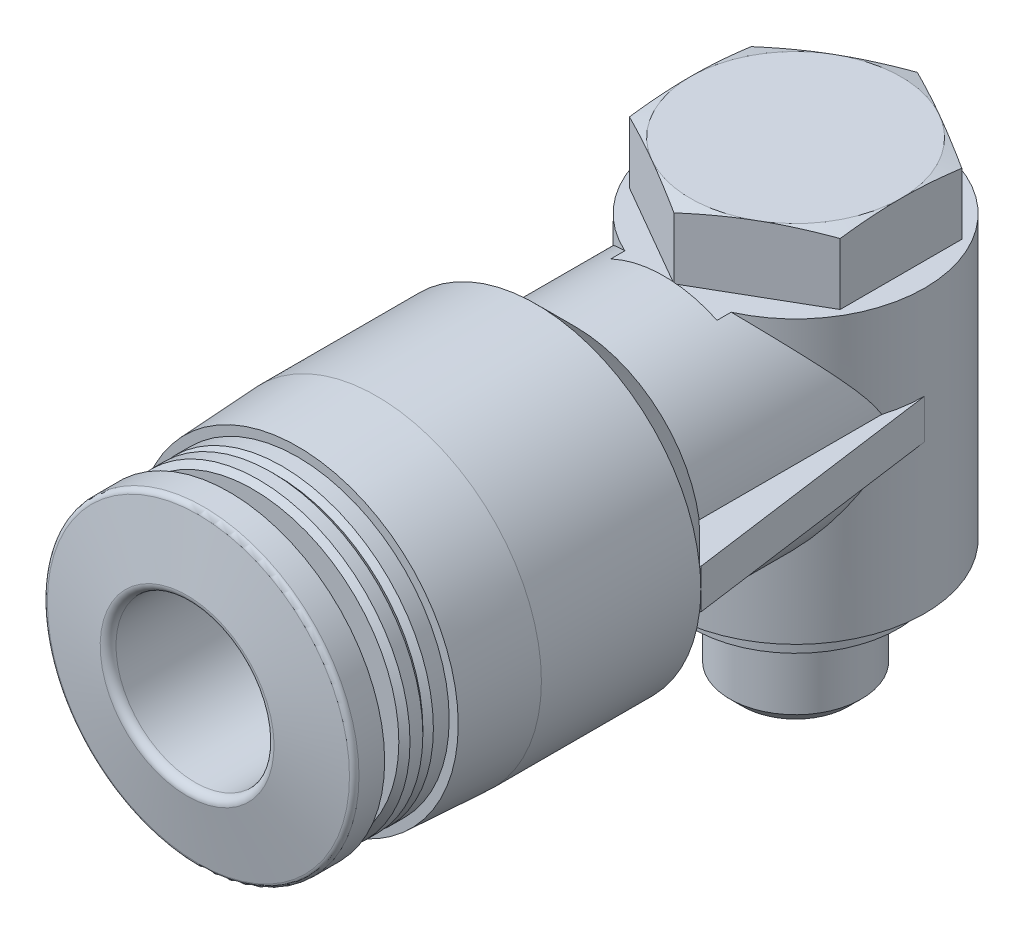
SolidWorks part; units mm, degrees
ref_plane "Ebene vorne" through (0, 0, 0) normal (0, 0, 1) x (1, 0, 0)
ref_plane "Ebene oben" through (0, 0, 0) normal (0, 1, 0) x (1, 0, 0)
ref_plane "Ebene rechts" through (0, 0, 0) normal (1, 0, 0) x (0, 0, -1)
sketch "Skizze1" plane through (0, 0, 0) normal (1, 0, 0) x (0, 0, -1)
  line L0 (0, 6.8) -> (4, 6.8)
  line L1 (4, 6.8) -> (4.9, 6.5588)
  line L2 (4.9, 6.5588) -> (4.9, -6.4)
  line L3 (4.9, -6.4) -> (3.4, -6.4)
  line L4 (3.4, -6.4) -> (3.4, -6.9)
  line L5 (3.4, -6.9) -> (3.9, -6.9)
  line L6 (3.9, -6.9) -> (3.9, -7.4)
  line L7 (3.9, -7.4) -> (2.5, -7.4)
  line L8 (2.5, -7.4) -> (2.5, -10.4095)
  line L9 (2.5, -10.4095) -> (2.0095, -10.9)
  line L10 (2.0095, -10.9) -> (0, -10.9)
  line L11 (0, -10.9) -> (0, 6.8)
  line L12 (0, -10.9) -> (0, 6.8) construction
revolve "Rotation1" add sketch "Skizze1" angle 360 about L12
cosmetic thread "Gewindedarstellung1" parameters "D1"=2.6504, "D2"=4.019
sketch "Skizze2" plane through (0, 0, 0) normal (1, 0, 0) x (0, 0, -1)
  line L0 (0, -4.75) -> (-8.35, -4.75)
  line L1 (-8.35, -4.75) -> (-9.85, -6.25)
  line L2 (-9.85, -6.25) -> (-15.9, -6.25)
  line L3 (-15.9, -6.25) -> (-18.9, -6.0928)
  line L4 (-18.9, -6.0928) -> (-18.9, -5.75)
  line L5 (-18.9, -5.75) -> (-19.5, -5.75)
  line L6 (-19.5, -5.75) -> (-19.7, -5.55)
  line L7 (-19.7, -5.55) -> (-19.9, -5.75)
  line L8 (-19.9, -5.75) -> (-20.3879, -5.75)
  line L9 (-20.3879, -5.75) -> (-20.6, -5.5379)
  line L10 (-20.6, -5.5379) -> (-20.6, -4.05)
  line L11 (-20.6, -4.05) -> (-21.3, -4.05)
  line L12 (-21.5, -4.25) -> (-21.5, -5.9)
  line L13 (-21.5, -5.9) -> (-22.4737, -5.9)
  line L14 (-22.6707, -5.7347) -> (-23.1, -3.3)
  line L15 (-23.1, -3.3) -> (-23.1, 0)
  line L16 (-23.1, 0) -> (4.75, 0)
  line L17 (-23.1, 0) -> (-15.9, 0) construction
  arc A0 (4.75, 0) -> (0, -4.75) centre (0, 0) cw
  arc A1 (-21.3, -4.05) -> (-21.5, -4.25) centre (-21.3, -4.25) ccw
  arc A2 (-22.4737, -5.9) -> (-22.6707, -5.7347) centre (-22.4737, -5.7) cw
revolve "Rotation2" add sketch "Skizze2" angle 360 about L17
sketch "Skizze3" plane through (0, 0, 0) normal (1, 0, 0) x (0, 0, -1)
  line L0 (0, -0.8) -> (-6.1, -0.8)
  line L1 (-6.1, -0.8) -> (-6.1, -3)
  line L2 (-6.1, -3) -> (-22.8, -3)
  line L3 (-23.1, -3.3) -> (-23.1, 0)
  line L4 (-23.1, 0) -> (0.8, 0)
  line L5 (-23.1, 0) -> (0, 0) construction
  arc A0 (0.8, 0) -> (0, -0.8) centre (0, 0) cw
  arc A1 (-22.8, -3) -> (-23.1, -3.3) centre (-22.8, -3.3) ccw
sketch "Skizze4" plane through (0, 0, 0) normal (0, 1, 0) x (1, 0, 0)
  line L0 (-6.25, -9.85) -> (6.25, -9.85)
  line L1 (6.25, -9.85) -> (4.9, 0)
  line L2 (4.9, 0) -> (-4.9, 0)
  line L3 (-4.9, 0) -> (-6.25, -9.85)
extrude "Linear austragen1" add sketch "Skizze4" against normal blind 0.75 and the other way blind 0.75
ref_plane "Ebene1" through (0, 4.3, 0) normal (0, 1, 0) x (-1, 0, 0)
sketch "Skizze5" plane through (0, 4.3, 0) normal (0, 1, 0) x (-1, 0, 0)
  line L0 (8, 5) -> (-8, 5)
  line L1 (-8, 5) -> (-8, -11)
  line L2 (-8, -11) -> (8, -11)
  line L3 (8, -11) -> (8, 5)
  line L4 (4, 2.3094) -> (0, 4.6188)
  line L5 (0, 4.6188) -> (-4, 2.3094)
  line L6 (-4, 2.3094) -> (-4, -2.3094)
  line L7 (-4, -2.3094) -> (0, -4.6188)
  line L8 (0, -4.6188) -> (4, -2.3094)
  line L9 (4, -2.3094) -> (4, 2.3094)
extrude "Linear austragen2" cut sketch "Skizze5" along normal blind 2.5
sketch "Skizze6" plane through (0, 0, 0) normal (1, 0, 0) x (0, 0, -1)
  line L0 (0, 0) -> (0.8, 0)
  line L1 (0.8, 0) -> (0.8, -10.9)
  line L2 (0.8, -10.9) -> (0, -10.9)
  line L3 (0, -10.9) -> (0, 0)
  line L4 (0, -10.9) -> (0, 0) construction
revolve "Schnitt-Rotation1" cut sketch "Skizze6" angle 360 about L4
ref_plane "Ebene2" through (0, 15.95, 0) normal (0, 1, 0) x (-1, 0, 0)
revolve "Schnitt-Rotation2" cut sketch "Skizze3" angle 360 about L5
